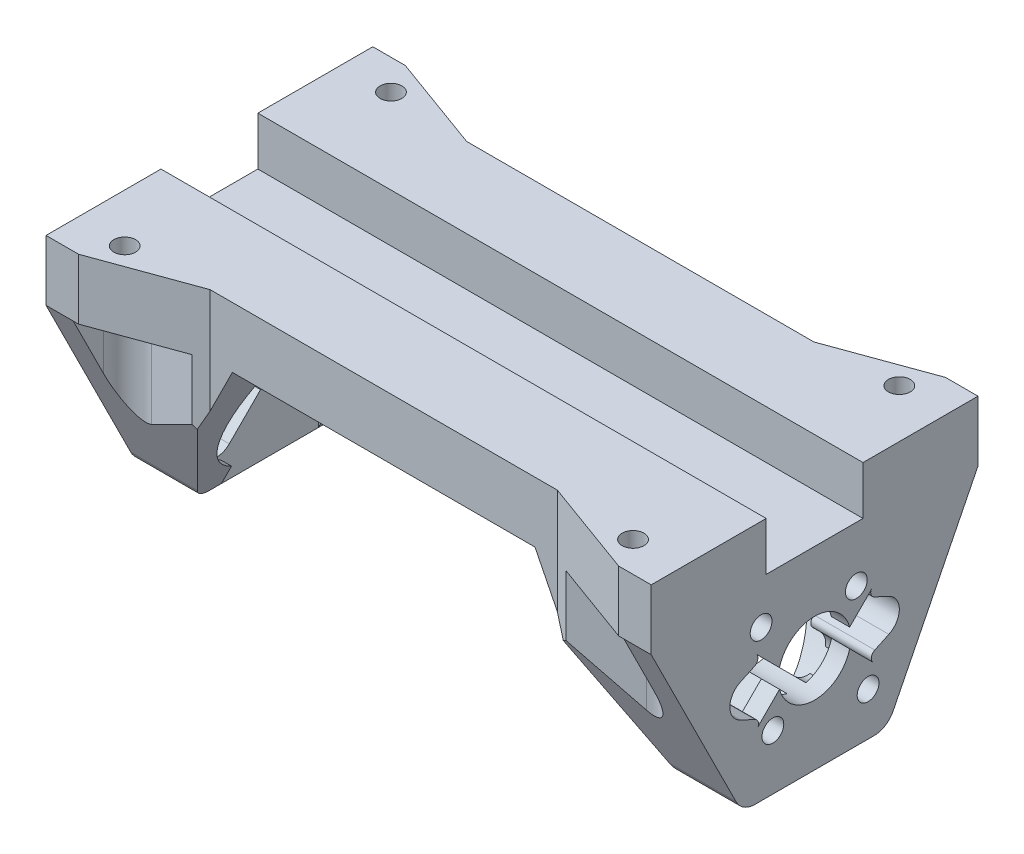
SolidWorks part; units mm, degrees
ref_plane "Front Plane" through (0, 0, 0) normal (0, 0, 1) x (1, 0, 0)
ref_plane "Top Plane" through (0, 0, 0) normal (0, 1, 0) x (1, 0, 0)
ref_plane "Right Plane" through (0, 0, 0) normal (1, 0, 0) x (0, 0, -1)
sketch "Sketch1" plane through (0, 0, 0) normal (0, 1, 0) x (1, 0, 0)
  line L0 (0, 0) -> (9.0185, 0) construction
  line L1 (-42, -22) -> (42, -22) construction
  line L2 (-42, -22) -> (-42, 22) construction
  line L3 (-42, 22) -> (42, 22) construction
  line L4 (42, -22) -> (42, 22) construction
  line L5 (-42, -22) -> (42, 22) construction
  line L6 (-42, 22) -> (42, -22) construction
  line L7 (0, 0) -> (0, 72.303) construction
  line L8 (50, 27) -> (-50, 27)
  line L9 (-50, -25) -> (-39.132, -25)
  line L10 (-50, -25) -> (-50, 25)
  line L11 (-50, 25) -> (-39.132, 25)
  line L12 (50, -25) -> (50, 25)
  line L13 (-50, -25) -> (50, 25) construction
  line L14 (-50, 25) -> (50, -25) construction
  line L15 (58.1438, 20.2) -> (0, 20.2) construction
  line L16 (-28.6916, 21.2) -> (28.6916, 21.2)
  line L17 (28.6916, 21.2) -> (44.6269, 27)
  line L18 (31.7917, 20.2) -> (57.8939, 29.7004) construction
  line L19 (50, 25) -> (50, 27)
  line L20 (-50, 25) -> (-50, 27)
  line L21 (50, -27) -> (-50, -27)
  line L22 (-28.6916, 21.2) -> (-44.6269, 27)
  line L23 (50, -25) -> (50, -27)
  line L24 (45.5, 22) -> (45.5, 27)
  line L25 (32.5087, -22.5893) -> (44.6269, -27)
  line L26 (-28.6916, -21.2) -> (32.5087, -22.5893)
  line L27 (-28.6916, -21.2) -> (-44.6269, -27)
  line L28 (40.8974, 18.6782) -> (30.8895, 22)
  line L29 (-50, -25) -> (-50, -27)
  line L30 (0, 21.2) -> (0, 27)
  line L31 (0, -21.2) -> (0, -27)
  line L32 (39.132, 25) -> (50, 25)
  line L33 (39.132, -25) -> (50, -25)
  line L34 (-50, 8) -> (50, 8)
  line L35 (-50, -8) -> (50, -8)
  circle A0 centre (42, 22) radius 1.8
  circle A1 centre (-42, 22) radius 1.8
  circle A2 centre (-42, -22) radius 1.8
  circle A3 centre (42, -22) radius 1.8
  arc A7 (40.8974, 18.6782) -> (45.5, 22) centre (42, 22) ccw
  arc A9 (40.8974, 18.6782) -> (45.5, 22) centre (42, 22) ccw
  point P0 (0, 0)
  point P29 (0, 27)
  point P34 (0, 21.2)
  point P48 (0, -8)
  point P49 (0, 8)
  dimension "D3" = 3.6
  dimension "D10" = 3.5
  dimension "D1" = 44
  dimension "D2" = 84
  dimension "D4" = 8
  dimension "D5" = 3
  dimension "D6" = 1
  dimension "D7" = 20
  dimension "D8" = 2
  dimension "D9" = 2
  dimension "D11" = 8
extrude "Boss-Extrude2" add sketch "Sketch1" along normal blind 10 contours A7 L28 L17 L16 L22 L11 L10 L34 L12 L32 L24 A1 | L28 A7 L24 L32 L17 A0 | L35 L10 L9 L27 L26 L25 L33 L12 A2 A3 | L10 L35 L12 L34 region at (-1.4817, 0, -14.9516) region at (39.5656, 0, -22.0349) region at (0, 0, 0) region at (0.2955, 0, 15.3833)
extrude "Boss-Extrude5" add sketch "Sketch1<8>" along normal up to surface (10 mm away) contours L11 L24 L8 L17 | L24 L11 L19 L8 region at (47.75, 0, -26) region at (43.3422, 0, -25.747) up to face at (0.3181, 10, 0.1158)
sketch "Sketch1<8>" plane through (0, 0, 0) normal (0, 1, 0) x (1, 0, 0) same geometry as "Sketch1"
mirror "Mirror10" about plane through (0, 0, 0) normal (0, 0, 1) of "Boss-Extrude5" second plane through (0, 0, 0) second plane normal (1, 0, 0)
sketch "Sketch2" plane through (0, 0, 0) normal (1, 0, 0) x (0, 0, -1)
  line L0 (-9.8369, -30) -> (9.8369, -30)
  line L1 (12, -30) -> (32.3221, 10.6441) construction
  line L2 (0, 0) -> (0, 31.9272) construction
  line L3 (25, 0) -> (-25, 0) construction
  line L4 (-200000, 0) -> (200072.303, 0) construction
  line L5 (27, 0) -> (12.9674, -28.0652)
  line L6 (-8, 2) -> (8, 2)
  line L7 (8, 2) -> (8, 10)
  line L8 (-27, 10) -> (27, 10) construction
  line L9 (-8, 2) -> (-8, 10)
  line L10 (8, 10) -> (-8, 10)
  line L11 (8, -26.6886) -> (8, -30)
  line L12 (12, 0) -> (12, -5)
  line L14 (-8, -26.6886) -> (-8, -30)
  line L15 (-27, 0) -> (-12.9674, -28.0652)
  line L16 (-12, 0) -> (-12, -5)
  line L17 (27, 0) -> (-27, 0)
  line L18 (27, 10) -> (27, 0) construction
  arc A0 (9.8369, -30) -> (12.9674, -28.0652) centre (9.8369, -26.5) ccw
  circle A1 centre (0, -14) radius 6
  circle A2 centre (0, -14) radius 15
  arc A3 (-9.8369, -30) -> (-12.9674, -28.0652) centre (-9.8369, -26.5) cw
  point P23 (0, 2)
  point P25 (0, 10)
  point P35 (0, -30)
  point P40 (0, 0)
  dimension "D3" = 3.5
  dimension "D4" = 14
  dimension "D5" = 12
  dimension "D8" = 30
  dimension "D1" = 30
  dimension "D2" = 12
  dimension "D6" = 2
  dimension "D7" = 8
  dimension "D9" = 8
  dimension "D10" = 15
sketch "Sketch4" plane through (50, 0, 0) normal (1, 0, 0) x (0, 0, -1)
  line L1 (27, 0) -> (12.9674, -28.0652) construction
  line L3 (27, 0) -> (12.9674, -28.0652)
  line L4 (-27, 0) -> (27, 0)
  line L6 (-27, 0) -> (27, 0)
  line L12 (0, 22.9537) -> (0, -14.1619) construction
  line L14 (-200000, 0) -> (200072.303, 0) construction
  line L16 (9.8369, -30) -> (-9.8369, -30)
  line L17 (-27, 0) -> (-12.9674, -28.0652)
  line L28 (27, 10) -> (-27, 10)
  line L32 (27, 10) -> (-27, 10)
  line L34 (27, 0) -> (27, 10)
  line L35 (27, 0) -> (27, 10)
  line L36 (-27, 10) -> (-27, 0)
  line L37 (-27, 10) -> (-27, 0)
  line L40 (27, 10) -> (27, 0) construction
  line L41 (-27, 0) -> (27, 0) construction
  arc A0 (9.8369, -30) -> (12.9674, -28.0652) centre (9.8369, -26.5) ccw construction
  arc A1 (9.8369, -30) -> (12.9674, -28.0652) centre (9.8369, -26.5) ccw
  circle A2 centre (0, -14) radius 6 construction
  circle A3 centre (0, -14) radius 6
  arc A10 (-9.8369, -30) -> (-12.9674, -28.0652) centre (-9.8369, -26.5) cw
  line B0 (0, -14) -> (25.7191, -14) construction
  line B1 (0, -14) -> (22.4503, -36.4503) construction
  line B2 (0, -14) -> (11.6935, -2.3065) construction
  line B3 (5.7956, -15.5529) -> (10.9602, -20.7175)
  line B4 (1.5529, -8.2044) -> (4.773, -4.9844)
  line B5 (5.7956, -12.4471) -> (9.0156, -9.227)
  line B6 (1.5529, -19.7956) -> (6.7175, -24.9602)
  line B7 (12.2679, -11.2811) -> (9.8501, -10.1536)
  line B8 (12.2679, -16.7189) -> (9.9434, -17.8028)
  circle B9 centre (11, -14) radius 1.2
  circle B10 centre (8.8388, -22.8388) radius 1.8
  circle B11 centre (6.8943, -7.1057) radius 1.8
  arc B12 (9.0156, -9.227) -> (4.773, -4.9844) centre (6.8943, -7.1057) ccw
  arc B13 (6.7175, -24.9602) -> (10.9602, -20.7175) centre (8.8388, -22.8388) ccw
  arc B14 (12.2679, -11.2811) -> (12.2679, -16.7189) centre (11, -14) cw
  arc B15 (9.8501, -10.1536) -> (9.4281, -8.7119) centre (10.2727, -9.2473) cw
  arc B16 (9.9434, -17.8028) -> (9.6589, -19.4163) centre (10.366, -18.7091) ccw
  line B17 (0, -14) -> (-25.7191, -14) construction
  line B18 (0, -14) -> (-22.4503, 8.4503) construction
  line B19 (0, -14) -> (-11.6935, -25.6935) construction
  line B20 (-5.7956, -12.4471) -> (-10.9602, -7.2825)
  line B21 (-1.5529, -19.7956) -> (-4.773, -23.0156)
  line B22 (-5.7956, -15.5529) -> (-9.0156, -18.773)
  line B23 (-1.5529, -8.2044) -> (-6.7175, -3.0398)
  line B24 (-12.2679, -16.7189) -> (-9.8501, -17.8464)
  line B25 (-12.2679, -11.2811) -> (-9.9434, -10.1972)
  circle B26 centre (-11, -14) radius 1.2
  circle B27 centre (-8.8388, -5.1612) radius 1.8
  circle B28 centre (-6.8943, -20.8943) radius 1.8
  arc B29 (-9.0156, -18.773) -> (-4.773, -23.0156) centre (-6.8943, -20.8943) ccw
  arc B30 (-6.7175, -3.0398) -> (-10.9602, -7.2825) centre (-8.8388, -5.1612) ccw
  arc B31 (-12.2679, -16.7189) -> (-12.2679, -11.2811) centre (-11, -14) cw
  arc B32 (-9.8501, -17.8464) -> (-9.4281, -19.2881) centre (-10.2727, -18.7527) cw
  arc B33 (-9.9434, -10.1972) -> (-9.6589, -8.5837) centre (-10.366, -9.2909) ccw
  line M5 (-27, 0) -> (27, 0)
  dimension "D4" = 45
  dimension "D1" = 0
sketch_block_instance "Block2-1"
sketch_block "Block2" parameters "D2"=2.4, "D4"=3.6, "D6"=3, "D8"=1, "D9"=1, "D1"=11, "D3"=12.5, "D5"=9.75, "D7"=25
sketch_block_instance "Block2-2"
extrude "Boss-Extrude6" add sketch "Sketch4" against normal blind 10 contours L6 L12 A3 B4 B12 B15 B7 B14 B8 B16 B3 B13 B6 L16 A1 L3 | L12 L17 A10 L16 A3 B21 B29 B32 B24 B31 B25 B33 B20 B30 B23 M5 region at (50, -13.7564, -19.4312)
extrude "Boss-Extrude7" add sketch "Sketch4<3>" against normal blind 3 contours B23 B30 B20 A3 B27 | B6 B13 B3 A3 B10 | B22 B29 B21 A3 B28 | B5 B12 B4 A3 B11 region at (50, -9.6739, -4.3261) region at (50, -20.9444, -6.9444) region at (50, -7.0556, 6.9444) region at (50, -21.3222, 3.2464)
sketch "Sketch4<3>" plane through (50, 0, 0) normal (1, 0, 0) x (0, 0, -1) same geometry as "Sketch4"
extrude "Boss-Extrude8" add sketch "Sketch4" against normal blind 6.7 contours L6 L12 A3 B4 B12 B15 B7 B14 B8 B16 B3 B13 B6 L16 A1 L3 | L12 L17 A10 L16 A3 B21 B29 B32 B24 B31 B25 B33 B20 B30 B23 M5 region at (50, -13.7564, -19.4312)
split "Split1" trim tools "Top Plane" bodies to split 184 resulting bodies 168 169
pattern_circular "CirPattern21" count 2 over 360 about axis through (0, 0, 0) along (0, 1, 0) reverse direction yes of bodies 169
extrude "Boss-Extrude13" add sketch "Sketch2" along normal through all and the other way through all contours A3 L0 L14 A2 L16 L17 L15 | A2 L11 L0 A0 L5 L17 L12 region at (0, -10.8734, 17.05) region at (0, -10.8734, -17.05)
sketch "Sketch11" plane through (0, 0, 0) normal (0, 0, 1) x (1, 0, 0)
  line L0 (0, 0) -> (0, -47.5532) construction
  line L1 (40, -30) -> (40, -26.6886) construction
  line L2 (40, -30) -> (40, -26.6886) construction
  line L3 (25, 0) -> (40, -30)
  line L4 (50, 0) -> (-50, 0) construction
  line L5 (-25, 0) -> (25, 0)
  line L6 (-40, -30) -> (40, -30)
  line L7 (50, -30) -> (-50, -30) construction
  line L8 (-25, 0) -> (-40, -30)
  point P13 (0, -30)
  point P14 (0, 0)
  dimension "D1" = 25
extrude "Cut-Extrude16" cut sketch "Sketch11" against normal through all both and the other way through all contours L5 L8 L6 L3 region at (0, -16.1538, 0)
extrude "Cut-Extrude17" cut sketch "Sketch1<16>" against normal through all both and the other way through all contours L30 L16 L17 L8 region at (18.6182, 0, -24.3101)
sketch "Sketch1<16>" plane through (0, 0, 0) normal (0, 1, 0) x (1, 0, 0) same geometry as "Sketch1"
extrude "Cut-Extrude18" cut sketch "Sketch1<17>" against normal through all contours L28 A7 L24 L32 L17 A0 | L17 L32 L24 L8 | A0 region at (43.3422, 0, -25.747) region at (39.5656, 0, -22.0349) region at (42, 0, -22)
sketch "Sketch1<17>" plane through (0, 0, 0) normal (0, 1, 0) x (1, 0, 0) same geometry as "Sketch1"
mirror "Mirror23" about plane through (0, 0, 0) normal (1, 0, 0) of "Cut-Extrude18", "Cut-Extrude17" second plane through (0, 0, 0) second plane normal (0, 0, 1)
extrude "Cut-Extrude19" cut sketch "Sketch1<18>" along normal through all from offset 2 contours L10 L35 L12 L34 region at (0, 0, 0)
sketch "Sketch1<18>" plane through (0, 0, 0) normal (0, 1, 0) x (1, 0, 0) same geometry as "Sketch1"
